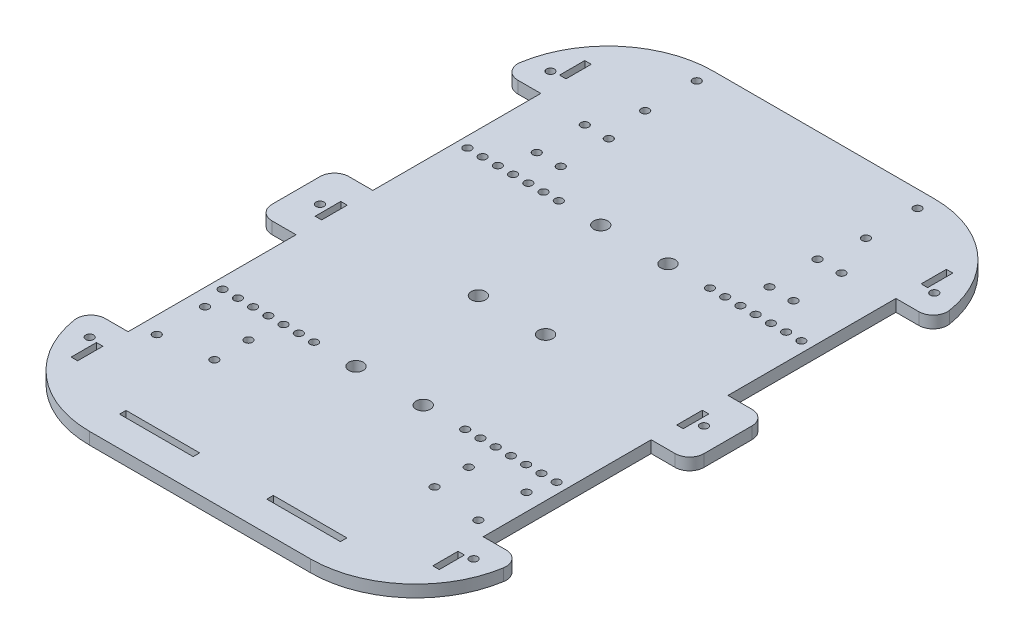
SolidWorks part; units mm, degrees
ref_plane "Ön Düzlem" through (0, 0, 0) normal (0, 0, 1) x (1, 0, 0)
ref_plane "Üst Düzlem" through (0, 0, 0) normal (0, 1, 0) x (1, 0, 0)
ref_plane "Sağ Düzlem" through (0, 0, 0) normal (1, 0, 0) x (0, 0, -1)
sketch "Sketch2" plane through (0, 0, 0) normal (0, 1, 0) x (1, 0, 0)
  line L0 (-74, -86) -> (-74, -51) construction
  line L1 (46, -130) -> (-46, -130)
  line L2 (90, -10) -> (90, 10)
  line L3 (46, 130) -> (-46, 130)
  line L4 (-90, -10) -> (-90, 10)
  line L5 (90, -130) -> (-90, 130) construction
  line L6 (90, 130) -> (-90, -130) construction
  line L7 (-83.5233, 86) -> (-74, 86)
  line L9 (-84, 16) -> (-74, 16)
  line L10 (-74, 86) -> (-74, 16)
  line L11 (-83.5233, -86) -> (-74, -86)
  line L13 (-84, -16) -> (-74, -16)
  line L14 (-74, -86) -> (-74, -16)
  line L15 (83.5233, 86) -> (74, 86)
  line L17 (84, 16) -> (74, 16)
  line L18 (74, 86) -> (74, 16)
  line L19 (83.5233, -86) -> (74, -86)
  line L21 (84, -16) -> (74, -16)
  line L22 (74, -86) -> (74, -16)
  line L23 (-74, 51) -> (74, 51) construction
  line L24 (-74, -51) -> (74, -51) construction
  line L26 (-74, 96.51) -> (-76.7, 96.51)
  line L27 (-76.7, 96.51) -> (-76.7, 107.02)
  line L28 (-74, 107.02) -> (-76.7, 107.02)
  line L29 (-74, 96.51) -> (-74, 107.02)
  line L30 (74, 96.51) -> (74, 107.02)
  line L31 (74, 107.02) -> (76.7, 107.02)
  line L32 (76.7, 96.51) -> (76.7, 107.02)
  line L33 (74, 96.51) -> (76.7, 96.51)
  line L34 (74, -107.02) -> (76.7, -107.02)
  line L35 (76.7, -96.51) -> (76.7, -107.02)
  line L36 (74, -96.51) -> (74, -107.02)
  line L37 (74, -96.51) -> (76.7, -96.51)
  line L38 (-74, -96.51) -> (-74, -107.02)
  line L39 (-74, -107.02) -> (-76.7, -107.02)
  line L40 (-76.7, -96.51) -> (-76.7, -107.02)
  line L41 (-74, -96.51) -> (-76.7, -96.51)
  line L42 (-74, 5.3333) -> (-74, -5.3333)
  line L43 (74, 5.3333) -> (74, -5.3333)
  line L44 (-74, 5.3333) -> (-76.7, 5.3333)
  line L45 (-76.7, 5.3333) -> (-76.7, -5.3333)
  line L46 (-76.7, -5.3333) -> (-74, -5.3333)
  line L47 (74, 5.3333) -> (76.7, 5.3333)
  line L48 (76.7, 5.3333) -> (76.7, -5.3333)
  line L49 (76.7, -5.3333) -> (74, -5.3333)
  line L52 (15.34, -117.53) -> (46.02, -117.53)
  line L54 (-15.34, -117.53) -> (-46.02, -117.53)
  line L56 (46.02, -117.53) -> (46.02, -114.83)
  line L57 (46.02, -114.83) -> (15.34, -114.83)
  line L59 (-15.34, -114.83) -> (-46.02, -114.83)
  line L60 (-46.02, -114.83) -> (-46.02, -117.53)
  line L62 (15.34, -117.53) -> (15.34, -114.83)
  line L63 (-15.34, -117.53) -> (-15.34, -114.83)
  arc A2 (-46, -130) -> (-89.4481, -92.9474) centre (-46, -86) cw
  arc A3 (-89.4481, 92.9474) -> (-46, 130) centre (-46, 86) cw
  arc A4 (89.4481, 92.9474) -> (46, 130) centre (46, 86) ccw
  arc A5 (89.4481, -92.9474) -> (46, -130) centre (46, -86) cw
  arc A6 (-84, 16) -> (-90, 10) centre (-84, 10) ccw
  arc A7 (-84, -16) -> (-90, -10) centre (-84, -10) cw
  arc A8 (90, 10) -> (84, 16) centre (84, 10) ccw
  arc A9 (90, -10) -> (84, -16) centre (84, -10) cw
  arc A10 (-89.4481, -92.9474) -> (-83.5233, -86) centre (-83.5233, -92) cw
  arc A11 (83.5233, -86) -> (89.4481, -92.9474) centre (83.5233, -92) cw
  arc A12 (-89.4481, 92.9474) -> (-83.5233, 86) centre (-83.5233, 92) ccw
  arc A13 (89.4481, 92.9474) -> (83.5233, 86) centre (83.5233, 92) cw
  point P0 (0, 0)
  point P34 (-90, -16)
  point P39 (90, -16)
  point P46 (-90, 86)
  point P49 (90, 86)
  dimension "D3" = 44
  dimension "D4" = 44
  dimension "D5" = 44
  dimension "D6" = 44
  dimension "D15" = 6
  dimension "D16" = 6
  dimension "D17" = 6
  dimension "D18" = 6
  dimension "D19" = 6
  dimension "D20" = 6
  dimension "D21" = 6
  dimension "D22" = 6
  dimension "D1" = 260
  dimension "D2" = 180
  dimension "D7" = 16
  dimension "D8" = 70
  dimension "D9" = 16
  dimension "D10" = 70
  dimension "D11" = 70
  dimension "D12" = 16
  dimension "D13" = 16
  dimension "D14" = 70
extrude "Boss-Extrude4" add sketch "Sketch2" along normal blind 5
sketch "Sketch5" plane through (0, 5, 0) normal (0, 1, 0) x (1, 0, 0)
  line L0 (-53.5, 63.83) -> (-43.5, 63.83) construction
  line L1 (-43.5, 63.83) -> (-43.5, 83.83) construction
  line L2 (-43.5, 83.83) -> (-43.5808, 83.8151) construction
  line L3 (-43.5808, 83.8151) -> (-53.5, 83.83) construction
  line L4 (-74, 86) -> (-74, 16) construction
  line L5 (53.5, 83.83) -> (43.5, 83.83) construction
  line L6 (43.5, 83.83) -> (43.5, 63.83) construction
  line L7 (43.5, 63.83) -> (53.5, 63.83) construction
  line L8 (74, 16) -> (74, 86) construction
  line L9 (46, 130) -> (-46, 130) construction
  circle A0 centre (-69.6, -51) radius 1.65
  circle A1 centre (-63.25, -51) radius 1.65
  circle A2 centre (-56.9, -51) radius 1.65
  circle A3 centre (-50.55, -51) radius 1.65
  circle A4 centre (-44.2, -51) radius 1.65
  circle A5 centre (-37.85, -51) radius 1.65
  circle A6 centre (-31.5, -51) radius 1.65
  circle A7 centre (31.5, -51) radius 1.65
  circle A8 centre (37.85, -51) radius 1.65
  circle A9 centre (44.2, -51) radius 1.65
  circle A10 centre (50.55, -51) radius 1.65
  circle A11 centre (56.9, -51) radius 1.65
  circle A12 centre (63.25, -51) radius 1.65
  circle A13 centre (69.6, -51) radius 1.65
  circle A14 centre (69.6, 51) radius 1.65
  circle A15 centre (63.25, 51) radius 1.65
  circle A16 centre (56.9, 51) radius 1.65
  circle A17 centre (50.55, 51) radius 1.65
  circle A18 centre (44.2, 51) radius 1.65
  circle A19 centre (37.85, 51) radius 1.65
  circle A20 centre (31.5, 51) radius 1.65
  circle A21 centre (-31.5, 51) radius 1.65
  circle A22 centre (-37.85, 51) radius 1.65
  circle A23 centre (-44.2, 51) radius 1.65
  circle A24 centre (-50.55, 51) radius 1.65
  circle A25 centre (-56.9, 51) radius 1.65
  circle A26 centre (-63.25, 51) radius 1.65
  circle A27 centre (-69.6, 51) radius 1.65
  circle A29 centre (-14, -51) radius 3
  circle A30 centre (14, -51) radius 3
  circle A31 centre (14, 51) radius 3
  circle A32 centre (-14, 51) radius 3
  circle A33 centre (-14, 0) radius 3
  circle A34 centre (14, 0) radius 3
  circle A35 centre (-80, 96) radius 1.65
  circle A36 centre (-80, 0) radius 1.65
  circle A37 centre (80, 0) radius 1.65
  circle A38 centre (-80, -96) radius 1.65
  circle A39 centre (80, -96) radius 1.65
  circle A40 centre (80, 96) radius 1.65
  circle A45 centre (-53.5, 83.83) radius 1.65
  circle A46 centre (-53.5, 63.83) radius 1.65
  circle A47 centre (-43.5, 63.83) radius 1.65
  circle A48 centre (-43.5, 83.83) radius 1.65
  circle A49 centre (43.5, 63.83) radius 1.65
  circle A50 centre (53.5, 63.83) radius 1.65
  circle A51 centre (43.5, 83.83) radius 1.65
  circle A52 centre (53.5, 83.83) radius 1.65
  circle A53 centre (-46, 123) radius 1.65
  circle A54 centre (-46, 101.5) radius 1.65
  circle A55 centre (46, 101.5) radius 1.65
  circle A56 centre (46, 123) radius 1.65
  circle A61 centre (-67, -60.96) radius 1.65
  circle A62 centre (-45.8971, -63.9231) radius 1.65
  circle A63 centre (-67, -81.04) radius 1.65
  circle A64 centre (-45.8971, -78.1568) radius 1.65
  circle A65 centre (45.8971, -63.9231) radius 1.65
  circle A66 centre (45.8971, -78.1568) radius 1.65
  circle A67 centre (67, -81.04) radius 1.65
  circle A68 centre (67, -60.96) radius 1.65
  dimension "D1" = 20.5
  dimension "D2" = 20.5
  dimension "D3" = 46.17
  dimension "D4" = 66.17
  dimension "D5" = 66.17
extrude "Cut-Extrude1" cut sketch "Sketch5" against normal through all
